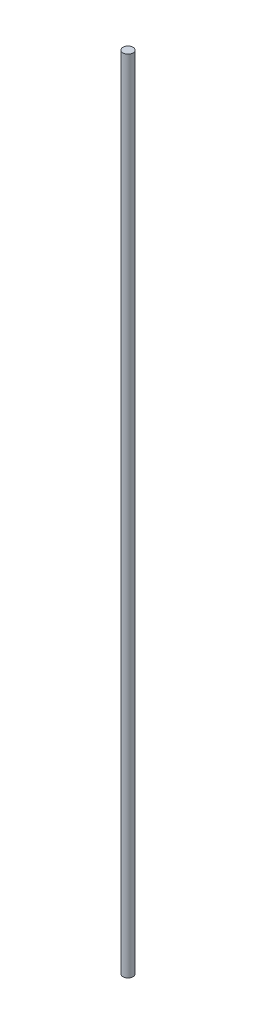
SolidWorks part; units mm, degrees
ref_plane "Front Plane" through (0, 0, 0) normal (0, 0, 1) x (1, 0, 0)
ref_plane "Top Plane" through (0, 0, 0) normal (0, 1, 0) x (1, 0, 0)
ref_plane "Right Plane" through (0, 0, 0) normal (1, 0, 0) x (0, 0, -1)
sketch "Sketch1" plane through (0, 0, 0) normal (0, 1, 0) x (1, 0, 0)
  circle A0 centre (0, 0) radius 2.5
  dimension "D1" = 5
extrude "Boss-Extrude1" add sketch "Sketch1" along normal blind 400
